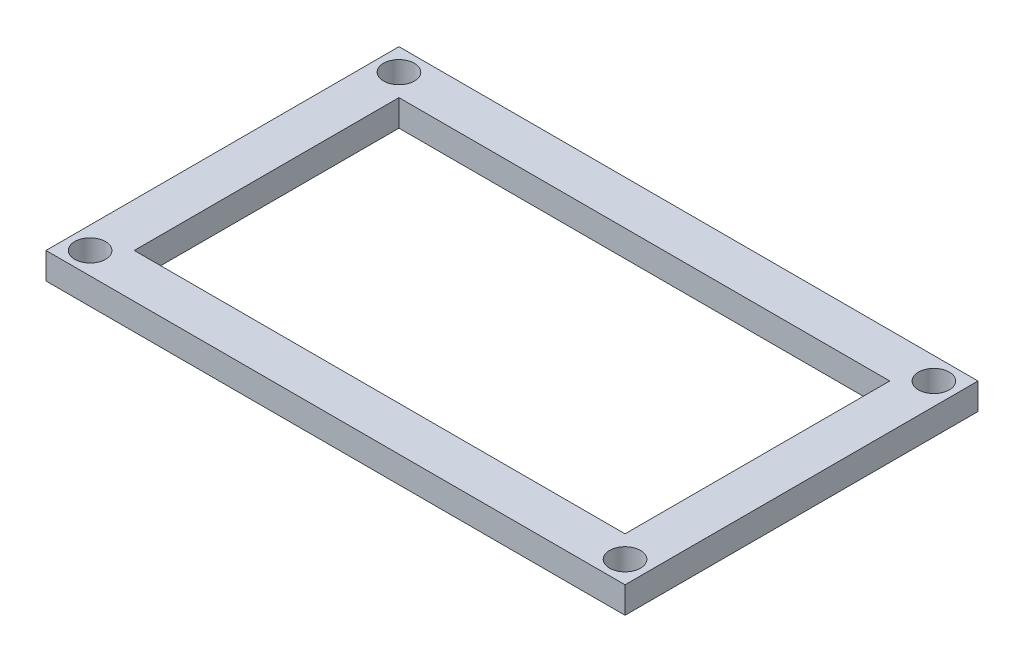
SolidWorks part; units mm, degrees
ref_plane "Alzado" through (0, 0, 0) normal (0, 0, 1) x (1, 0, 0)
ref_plane "Planta" through (0, 0, 0) normal (0, 1, 0) x (1, 0, 0)
ref_plane "Vista lateral" through (0, 0, 0) normal (1, 0, 0) x (0, 0, -1)
sketch "Croquis1" plane through (0, 0, 0) normal (0, 1, 0) x (1, 0, 0)
  line L0 (30.3109, 0) -> (-30.3109, 0) construction
  line L5 (30.3109, 0) -> (-30.3109, 0) construction
  line L6 (30.3109, 0) -> (30.3109, -35) construction
  line L7 (30.3109, 0) -> (30.3109, -35) construction
  line L8 (27.8109, -2.5) -> (-27.8109, -2.5)
  line L9 (-27.8109, -2.5) -> (-27.8109, -32.5)
  line L10 (-27.8109, -32.5) -> (27.8109, -32.5)
  line L11 (27.8109, -32.5) -> (27.8109, -2.5)
  line L12 (32.8109, 2.5) -> (-32.8109, 2.5)
  line L13 (-32.8109, 2.5) -> (-32.8109, -37.5)
  line L14 (-32.8109, -37.5) -> (32.8109, -37.5)
  line L15 (32.8109, -37.5) -> (32.8109, 2.5)
  line L16 (30.3109, -35) -> (-30.3109, -35) construction
  line L17 (-30.3109, -35) -> (-30.3109, 0) construction
  circle A1 centre (30.3109, 0) radius 1.75
  circle A12 centre (-30.3109, 0) radius 1.75
  circle A13 centre (-30.3109, -35) radius 1.75
  circle A14 centre (30.3109, -35) radius 1.75
  point P4 (0, 0)
  point P19 (49.4975, 0)
  point P21 (27.8109, -17.5)
  dimension "D1" = 3.5
  dimension "D4" = 2.5
  dimension "D5" = 2.5
  dimension "D2" = 2.5
  dimension "D3" = 2.5
  dimension "D6" = 2.5
  dimension "D7" = 2.5
  dimension "D8" = 2.5
  dimension "D9" = 2.5
extrude "Saliente-Extruir1" add sketch "Croquis1" along normal blind 3
